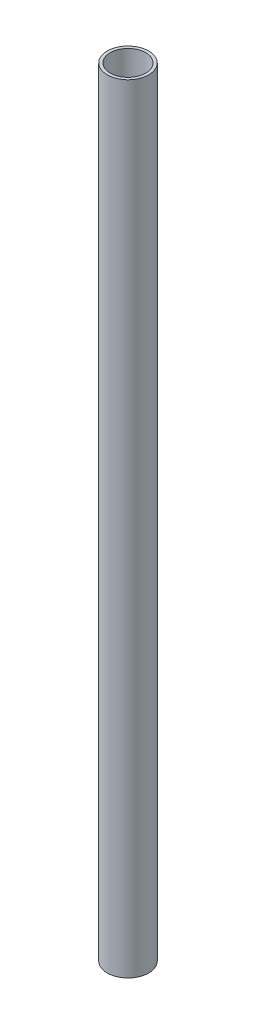
SolidWorks part; units mm, degrees
ref_plane "Front Plane" through (0, 0, 0) normal (0, 0, 1) x (1, 0, 0)
ref_plane "Top Plane" through (0, 0, 0) normal (0, 1, 0) x (1, 0, 0)
ref_plane "Right Plane" through (0, 0, 0) normal (1, 0, 0) x (0, 0, -1)
sketch "Sketch1" plane through (0, 0, 0) normal (0, 1, 0) x (1, 0, 0)
  circle A0 centre (0, 0) radius 0.5321
  circle A1 centre (0, 0) radius 0.4559
  dimension "D1" = 1.0643
  dimension "D2" = 0.0762
extrude "Boss-Extrude1" add sketch "Sketch1" along normal blind 20
